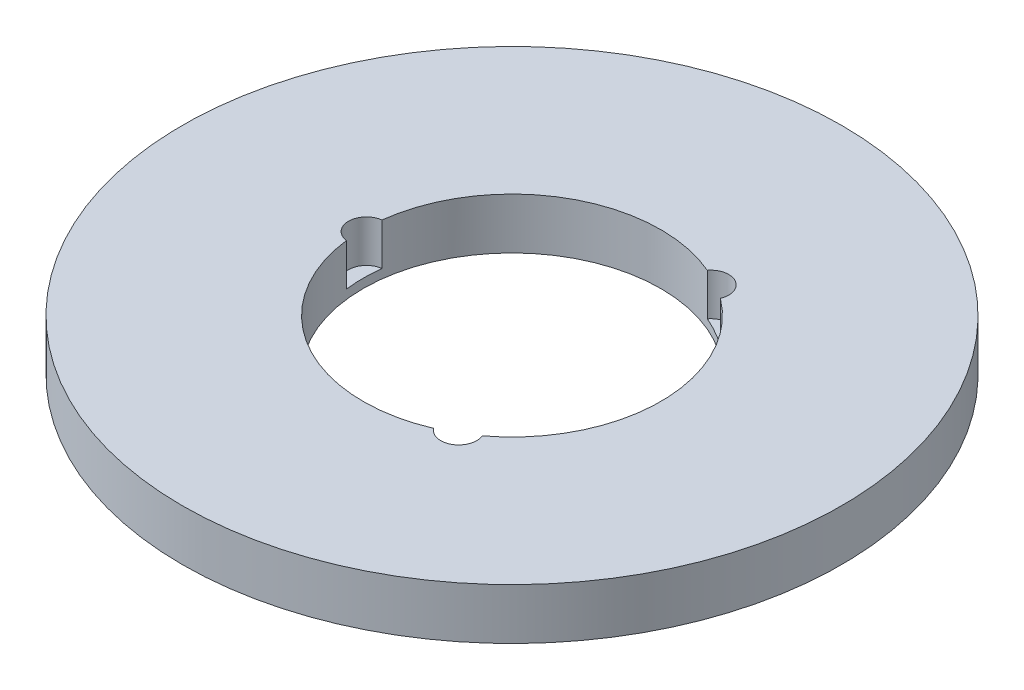
SolidWorks part; units mm, degrees
ref_plane "Front Plane" through (0, 0, 0) normal (0, 0, 1) x (1, 0, 0)
ref_plane "Top Plane" through (0, 0, 0) normal (0, 1, 0) x (1, 0, 0)
ref_plane "Right Plane" through (0, 0, 0) normal (1, 0, 0) x (0, 0, -1)
sketch "Sketch1" plane through (0, 0, 0) normal (0, 1, 0) x (1, 0, 0)
  circle A0 centre (0, 0) radius 77.5
  dimension "FLANGE_OD" = 155
extrude "Boss-Extrude1" add sketch "Sketch1" along normal blind 12
sketch "Sketch2" plane through (0, 0, 0) normal (0, 1, 0) x (1, 0, 0)
  circle A0 centre (0, 0) radius 35
  dimension "BORE_D" = 70
extrude "Cut-Extrude1" cut sketch "Sketch2" along normal through all
sketch "Sketch3" plane through (0, 12, 0) normal (0, 1, 0) x (1, 0, 0)
  circle A0 centre (0, 0) radius 34.2253 construction
  circle A1 centre (-34.2253, 0) radius 4.216
  dimension "BOLT_D" = 8.4319
  dimension "BOLT_PCD" = 68.4507
extrude "Cut-Extrude2" cut sketch "Sketch3" against normal blind 9.8868
pattern_circular "CirPattern1" count 3 over 360 about axis through (0, 0, 0) along (0, 1, 0) of "Cut-Extrude2"
